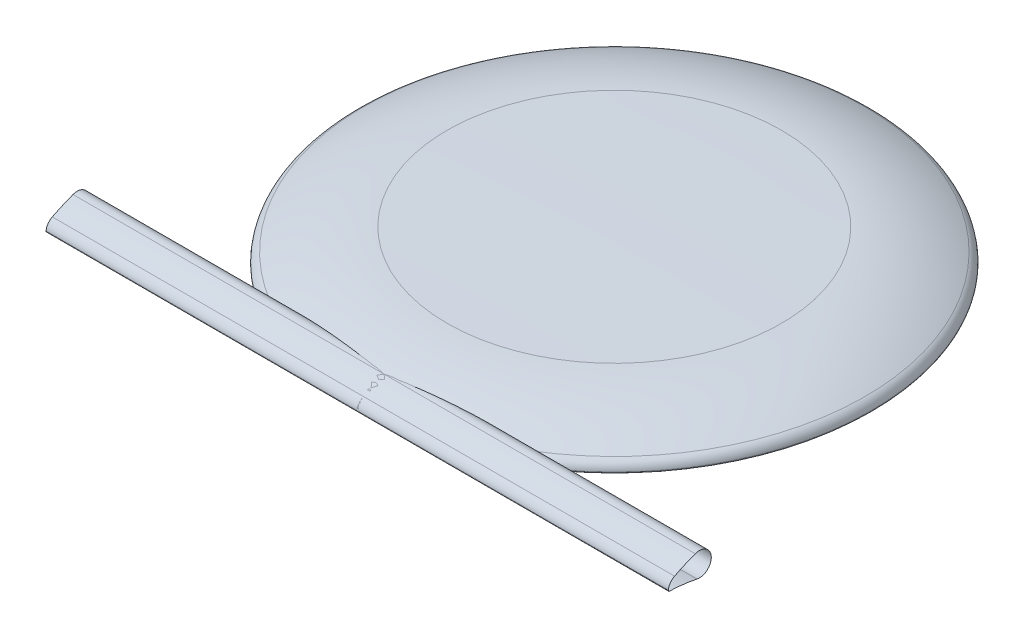
SolidWorks part; units mm, degrees
note: '?' marks a value the reader was unsure of.
other "Camera1"
ref_plane "Front" through (0, 0, 0) normal (0, 0, 1) x (1, 0, 0)
ref_plane "Top" through (0, 0, 0) normal (0, 1, 0) x (1, 0, 0)
ref_plane "Right" through (0, 0, 0) normal (1, 0, 0) x (0, 0, -1)
ref_axis "X" through (-80.9, 0, 0) along (1, 0, 0)?
ref_axis "Y" through (0, 50, 0) along (0, -1, 0)?
ref_axis "Z" through (0, 0, 50) along (0, 0, -1)?
sketch "Sketch1" plane through (0, 0, 0) normal (1, 0, 0) x (0, 0, -1)
  line L0 (-82, -9.5) -> (-82, 3.4431)
  line L1 (105, -9.5) -> (-105, -9.5) construction
  line L2 (105, -9.5) -> (105, 9.5) construction
  line L3 (105, 9.5) -> (-105, 9.5) construction
  line L4 (-105, -9.5) -> (-105, 9.5) construction
  line L5 (105, -9.5) -> (-105, 9.5) construction
  line L6 (105, 9.5) -> (-105, -9.5) construction
  line L7 (0, 0) -> (0, 20.6419) construction
  line L8 (0, 9.5) -> (0, 7.0844)
  line L9 (0, 7.0844) -> (-3.175, 7.0844)
  line L10 (-3.175, 7.0844) -> (-3.175, 6.9574)
  line L12 (0, 41.348) -> (-130.0496, 41.348)
  line L13 (0, 41.348) -> (0, -36.725)
  line L14 (0, -36.725) -> (-130.0496, -36.725)
  line L15 (-130.0496, 41.348) -> (-130.0496, -36.725)
  arc A0 (0, 9.5) -> (-68.2625, 8.3094) centre (0, -1947.9536) ccw
  arc A1 (-82, -9.5) -> (-105, -4.7375) centre (-106.5875, -70.3235) ccw
  arc A2 (-105, -4.7375) -> (-102.3936, -0.491) centre (-100.2375, -4.7375) cw
  arc A3 (-102.3936, -0.491) -> (-68.2625, 8.3094) centre (-65.4139, -73.325) cw
  arc A4 (-3.175, 6.9574) -> (-12.573, 6.9196) centre (0, -1947.9536) ccw
  arc A5 (-81.3918, 4.1894) -> (-68.1739, 5.7709) centre (-65.4139, -73.325) cw
  arc A6 (-101.2437, -2.7558) -> (-68.1739, 5.7709) centre (-65.4139, -73.325) cw construction
  arc A7 (-82, 3.4431) -> (-81.3918, 4.1894) centre (-81.238, 3.4431) cw
  arc A8 (-12.827, 6.9179) -> (-12.573, 6.9196) centre (-12.7, 6.9187) ccw
  arc A9 (-12.827, 6.9179) -> (-68.1739, 5.7709) centre (0, -1947.9536) ccw
  arc A10 (0, 6.96) -> (-68.1739, 5.7709) centre (0, -1947.9536) ccw construction
  point P0 (0, 0)
  dimension "D1" = 210
  dimension "D3" = 23
  dimension "D6" = 2.54
  dimension "D7" = 0.762
  dimension "D9" = 4.7625
  dimension "D11" = 0.254
  dimension "D12" = 0.127
  dimension "D2" = 19
  dimension "D4" = 4.7625
  dimension "D5" = 1.5875
  dimension "D8" = 136.525
  dimension "D10" = 2.3813
  dimension "D13" = 25.4
  dimension "D14" = 6.35
  dimension "D15" = 0.127
  dimension "D16" = 12.9431
revolve "Revolve1" add sketch "Sketch1" angle 360 about L7
fillet "Fillet1" radius 0.508 2 edges at (0, -9.5, -82) (0, -4.7375, -105)
sketch "Sketch2" plane through (0, 0, 0) normal (1, 0, 0) x (0, 0, -1)
  arc A0 (-93.2538, -6.0876) -> (-93.9634, 3.2074) centre (-92.2679, -1.3377) ccw
  arc A1 (-68.2625, 8.3094) -> (-102.3936, -0.491) centre (-65.4139, -73.325) ccw construction
  arc A2 (-82.693, -9.2244) -> (-104.4797, -4.7522) centre (-106.5875, -70.3235) ccw construction
  arc A3 (-82.693, -9.2244) -> (-104.4797, -4.7522) centre (-106.5875, -70.3235) ccw construction
  arc A4 (-104.9679, -4.1855) -> (-104.4797, -4.7522) centre (-104.4633, -4.2444) ccw construction
  arc A5 (-102.3936, -0.491) -> (-104.9679, -4.1855) centre (-100.2375, -4.7375) ccw construction
  arc A6 (-68.2625, 8.3094) -> (-102.3936, -0.491) centre (-65.4139, -73.325) ccw construction
  arc A7 (-93.2538, -6.0876) -> (-104.4797, -4.7522) centre (-106.5875, -70.3235) ccw
  arc A8 (-104.9679, -4.1855) -> (-104.4797, -4.7522) centre (-104.4633, -4.2444) ccw
  arc A9 (-102.3936, -0.491) -> (-104.9679, -4.1855) centre (-100.2375, -4.7375) ccw
  arc A10 (-93.9634, 3.2074) -> (-102.3936, -0.491) centre (-65.4139, -73.325) ccw
  dimension "D1" = 12.7
surface "Surface-Extrude1" sketch "Sketch2" parameters "D1"=254
split "Split1" trimming surface bodies 153 bodies to split 101 resulting bodies 155 156
